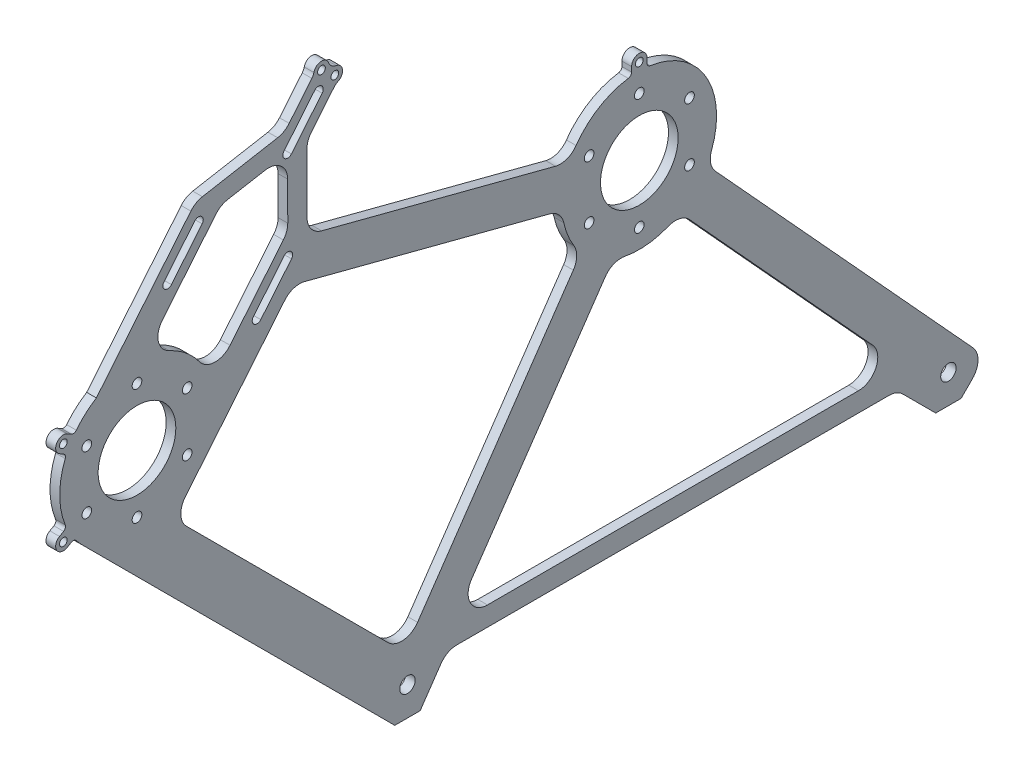
SolidWorks part; units mm, degrees
material "Stal węglowa"
ref_plane "Front" through (0, 0, 0) normal (0, 0, 1) x (1, 0, 0)
ref_plane "Top" through (0, 0, 0) normal (0, 1, 0) x (1, 0, 0)
ref_plane "Right" through (0, 0, 0) normal (1, 0, 0) x (0, 0, -1)
sketch "Szkic1" plane through (0, 0, 0) normal (1, 0, 0) x (0, 0, -1)
  line L316 (-288.2843, -28.2843) -> (-126.5685, -190)
  line L317 (-126.5685, -190) -> (-113.4315, -190)
  line L318 (113.431, -160) -> (-78.6067, -160)
  line L319 (-230.1276, 87.8475) -> (-246.042, 68.5661)
  line L320 (-226.2715, 84.6648) -> (-242.1858, 65.3833)
  line L321 (-180.0153, 45.8513) -> (-195.9297, 26.5698)
  line L322 (-168.0227, 115.3651) -> (-183.937, 96.0837)
  line L323 (-164.1665, 112.1824) -> (-180.0808, 92.9009)
  line L324 (-183.8715, 49.034) -> (-199.7858, 29.7526)
  line L325 (-232.1109, 93.2994) -> (-281.0377, 34.0208)
  line L326 (-219.1359, 85.4552) -> (-246.8933, 51.825)
  line L327 (-181.9648, 62.8067) -> (-181.9923, 82.5684)
  line L328 (-213.179, 88.9344) -> (-193.7477, 92.3992)
  line L329 (-184.2525, 56.4273) -> (-211.8302, 23.0147)
  line L330 (-169.4763, 121.4588) -> (-181.2419, 107.2038)
  line L331 (-157.9078, 111.9105) -> (-169.7167, 97.6031)
  line L332 (-43.4296, 19.0753) -> (-164.4845, 50.6409)
  line L333 (-171.9613, 60.3035) -> (-172.0044, 91.2236)
  line L334 (172.6968, -170.3622) -> (39.3548, -24.5194)
  line L335 (-234.3964, -46.8168) -> (-130.096, -151.1172)
  line L336 (-226.154, 96.7786) -> (-187.1989, 103.7246)
  line L337 (120.8113, -143.2523) -> (26.0693, -39.6282)
  line L338 (-113.4315, -190) -> (-102.6964, -174.3447)
  line L339 (172.3875, -184.181) -> (166.5685, -190)
  line L340 (153.4315, -190) -> (166.5685, -190)
  line L341 (136.3604, -172.9289) -> (153.4315, -190)
  line L342 (-94.4491, -170) -> (129.2893, -170)
  line L343 (-114.7776, -149.7014) -> (-34.1631, -32.1385)
  line L344 (-86.854, -144.3447) -> (-17.6685, -43.4491)
  line L345 (-298, -17.3205) -> (-300.1051, -18.5359)
  line L346 (-294, -24.2487) -> (-296.1051, -25.4641)
  line L347 (-298, 17.3205) -> (-300.1051, 18.5359)
  line L348 (-294, 24.2487) -> (-296.1051, 25.4641)
  line L349 (4, 41.5692) -> (4, 44)
  line L350 (-4, 41.5692) -> (-4, 44)
  line L351 (-183.5753, 28.9703) -> (-235.0376, -33.3802)
  line L352 (-46.3607, -0.8292) -> (-173.3398, 32.2813)
  arc A186 (-7.537, -39.2835) -> (14.9512, -37.1007) centre (0, 0) ccw
  arc A187 (-227.634, 23.5041) -> (-243.3448, 36.3676) centre (-260, 0) ccw
  circle A188 centre (-285.9808, -15) radius 2.5
  circle A189 centre (-234.0192, -15) radius 2.5
  circle A190 centre (-260, -30) radius 2.5
  circle A191 centre (-234.0192, 15) radius 2.5
  circle A192 centre (-260, 30) radius 2.5
  circle A193 centre (-285.9808, 15) radius 2.5
  circle A194 centre (-25.9808, -15) radius 2.5
  circle A195 centre (0, 30) radius 2.5
  circle A196 centre (25.9808, -15) radius 2.5
  circle A197 centre (-25.9808, 15) radius 2.5
  circle A198 centre (0, -30) radius 2.5
  circle A199 centre (25.9808, 15) radius 2.5
  circle A200 centre (160, -175) radius 4
  circle A201 centre (-120, -175) radius 4
  arc A202 (-226.2715, 84.6648) -> (-230.1276, 87.8475) centre (-228.1995, 86.2562) ccw
  arc A203 (-199.7858, 29.7526) -> (-195.9297, 26.5698) centre (-197.8578, 28.1612) ccw
  arc A204 (-164.1665, 112.1824) -> (-168.0227, 115.3651) centre (-166.0946, 113.7738) ccw
  arc A205 (-183.937, 96.0837) -> (-180.0808, 92.9009) centre (-182.0089, 94.4923) ccw
  arc A206 (-180.0153, 45.8513) -> (-183.8715, 49.034) centre (-181.9434, 47.4427) ccw
  arc A207 (-246.042, 68.5661) -> (-242.1858, 65.3833) centre (-244.1139, 66.9747) ccw
  arc A208 (-281.0377, 34.0208) -> (-291.4286, 24.7436) centre (-260, 0) ccw
  arc A209 (-181.9923, 82.5684) -> (-193.7477, 92.3992) centre (-191.9923, 82.5545) ccw
  circle A210 centre (-157.5969, 117) radius 2
  arc A211 (-156.0212, 113.3234) -> (-156.9343, 120.9447) centre (-157.5969, 117) ccw
  arc A212 (37.388, -14.2174) -> (39.3548, -24.5194) centre (46.7351, -17.7717) ccw
  arc A213 (-169.7167, 97.6031) -> (-172.0044, 91.2236) centre (-162.0044, 91.2375) ccw
  arc A214 (-43.4296, 19.0753) -> (-32.7252, 23.0014) centre (-40.9065, 28.7517) ccw
  arc A215 (172.3875, -184.181) -> (172.6968, -170.3622) centre (165.3165, -177.1099) ccw
  arc A216 (-246.8933, 51.825) -> (-243.3448, 36.3676) centre (-239.1809, 45.4595) ccw
  arc A217 (-171.9613, 60.3035) -> (-164.4845, 50.6409) centre (-161.9613, 60.3174) ccw
  arc A218 (-39.1071, -8.4045) -> (-33.9283, -21.1866) centre (0, 0) ccw
  arc A219 (26.0693, -39.6282) -> (14.9512, -37.1007) centre (18.689, -46.3759) ccw
  arc A220 (37.388, -14.2174) -> (5.7143, 39.5897) centre (0, 0) ccw
  arc A221 (-94.4491, -170) -> (-102.6964, -174.3447) centre (-94.4491, -180) ccw
  arc A222 (-187.1989, 103.7246) -> (-181.2419, 107.2038) centre (-188.9542, 113.5693) ccw
  arc A223 (-226.154, 96.7786) -> (-232.1109, 93.2994) centre (-224.3986, 86.9339) ccw
  arc A224 (-184.2525, 56.4273) -> (-181.9648, 62.8067) centre (-191.9648, 62.7928) ccw
  arc A225 (-213.179, 88.9344) -> (-219.1359, 85.4552) centre (-211.4236, 79.0897) ccw
  arc A226 (136.3604, -172.9289) -> (129.2893, -170) centre (129.2893, -180) ccw
  arc A227 (-227.634, 23.5041) -> (-211.8302, 23.0147) centre (-219.5426, 29.3802) ccw
  arc A228 (-86.854, -144.3447) -> (-78.6067, -160) centre (-78.6067, -150) ccw
  arc A229 (-130.096, -151.1172) -> (-114.7776, -149.7014) centre (-123.0249, -144.0462) ccw
  arc A230 (-7.537, -39.2835) -> (-17.6685, -43.4491) centre (-9.4212, -49.1044) ccw
  arc A231 (-34.1631, -32.1385) -> (-33.9283, -21.1866) centre (-42.4103, -26.4833) ccw
  circle A232 centre (-298.1051, 22) radius 2
  arc A233 (-294, 24.2487) -> (-291.4286, 24.7436) centre (-293, 25.9808) ccw
  arc A234 (-297.1429, 14.8461) -> (-297.1429, -14.8461) centre (-260, 0) ccw
  arc A235 (-296.1051, 25.4641) -> (-300.1051, 18.5359) centre (-298.1051, 22) ccw
  arc A236 (-291.4286, -24.7436) -> (-288.2843, -28.2843) centre (-260, 0) ccw
  arc A237 (-291.4286, -24.7436) -> (-294, -24.2487) centre (-293, -25.9808) ccw
  circle A238 centre (-298.1051, -22) radius 2
  arc A239 (-300.1051, -18.5359) -> (-296.1051, -25.4641) centre (-298.1051, -22) ccw
  arc A240 (-298, -17.3205) -> (-297.1429, -14.8461) centre (-299, -15.5885) ccw
  arc A241 (-297.1429, 14.8461) -> (-298, 17.3205) centre (-299, 15.5885) ccw
  arc A242 (-5.7143, 39.5897) -> (-4, 41.5692) centre (-6, 41.5692) ccw
  circle A243 centre (0, 44) radius 2
  arc A244 (4, 44) -> (-4, 44) centre (0, 44) ccw
  arc A245 (4, 41.5692) -> (5.7143, 39.5897) centre (6, 41.5692) ccw
  arc A246 (-5.7143, 39.5897) -> (-32.7252, 23.0014) centre (0, 0) ccw
  arc A247 (-235.0376, -33.3802) -> (-234.3964, -46.8168) centre (-227.3253, -39.7458) ccw
  arc A248 (113.431, -160) -> (120.8113, -143.2523) centre (113.431, -150) ccw
  arc A249 (-173.3398, 32.2813) -> (-183.5753, 28.9703) centre (-175.863, 22.6048) ccw
  arc A250 (-39.1071, -8.4045) -> (-46.3607, -0.8292) centre (-48.8839, -10.5056) ccw
  arc A251 (-156.0212, 113.3234) -> (-157.9078, 111.9105) centre (-154.0516, 108.7277) ccw
  arc A252 (-169.4763, 121.4588) -> (-168.4467, 123.579) centre (-173.3325, 124.6415) ccw
  arc A253 (-160.7905, 124.1275) -> (-156.9343, 120.9447) centre (-156.106, 125.8757) ccw
  arc A254 (-160.7905, 124.1275) -> (-168.4467, 123.579) centre (-164.538, 122.729) ccw
  circle A255 centre (-164.538, 122.729) radius 2
  circle A256 centre (0, 0) radius 20.1
  circle A257 centre (-260, 0) radius 20.1
extrude "Dodanie-wyciągnięcie1" add sketch "Szkic1" along normal blind 5
